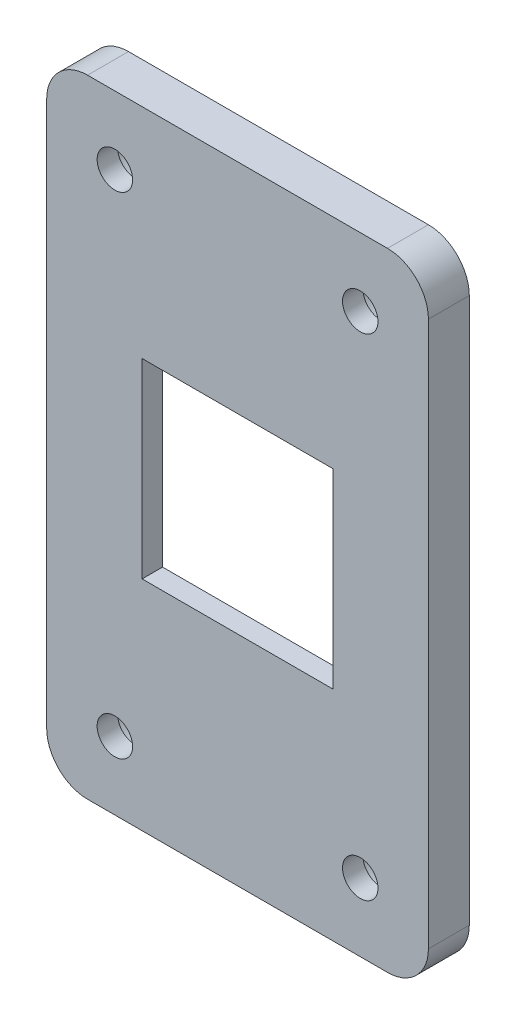
SolidWorks part; units mm, degrees
ref_plane "Front Plane" through (0, 0, 0) normal (1, 0, 0) x (0, 1, 0)
ref_plane "Top Plane" through (0, 0, 0) normal (0, 0, 1) x (0, 1, 0)
ref_plane "Right Plane" through (0, 0, 0) normal (0, 1, 0) x (-1, 0, 0)
sketch "Sketch2" plane through (0, 0, 0) normal (0, 0, 1) x (0, 1, 0)
  line L0 (-10, 10) -> (10, 10)
  line L1 (18, 9) -> (-18, 9) construction
  line L2 (18, 9) -> (18, -9) construction
  line L3 (18, -9) -> (-18, -9) construction
  line L4 (-18, 9) -> (-18, -9) construction
  line L5 (18, 9) -> (-18, -9) construction
  line L6 (18, -9) -> (-18, 9) construction
  line L7 (23, 14) -> (-23, 14)
  line L8 (23, 14) -> (23, -14)
  line L9 (23, -14) -> (-23, -14)
  line L10 (-23, 14) -> (-23, -14)
  line L11 (23, 14) -> (-23, -14) construction
  line L12 (23, -14) -> (-23, 14) construction
  line L13 (-7, 7) -> (7, 7)
  line L14 (-7, 7) -> (-7, -7)
  line L15 (-7, -7) -> (7, -7)
  line L16 (7, 7) -> (7, -7)
  line L17 (-7, 7) -> (7, -7) construction
  line L18 (-7, -7) -> (7, 7) construction
  line L19 (10, 10) -> (10, -10)
  line L20 (-10, -10) -> (10, -10)
  line L21 (-10, 10) -> (-10, -10)
  circle A0 centre (-18, 9) radius 2.5
  circle A1 centre (18, 9) radius 2.5
  circle A2 centre (18, -9) radius 2.5
  circle A3 centre (-18, -9) radius 2.5
  point P0 (0, 0)
  point P6 (0, 0)
  point P16 (0, 0)
  dimension "D5" = 5
  dimension "D1" = 36
  dimension "D2" = 18
  dimension "D3" = 5
  dimension "D4" = 5
  dimension "D6" = 14
  dimension "D7" = 3
extrude "Boss-Extrude1" add sketch "Sketch2" along normal blind 3 contours A3 | L7 L10 L9 L8 A3 A2 A1 A0 | A0 | A1 | A2 | L0 L21 L20 L19 L13 L16 L15 L14 region at (-9.7172, 0, 0) region at (0, 22.4615, 0) region at (-9, -18, 0) region at (-9, 18, 0) region at (9, 18, 0) region at (9, -18, 0)
hole_wizard "Ø2.6 (2.6) Diameter Hole1" positions "Sketch4" profile "Sketch5" hole size "Ø2.6" standard "ANSI Metric" end condition through all
sketch "Sketch4" plane through (0, 0, 0) normal (0, 0, -1) x (-1, 0, 0)
  point P0 (-9, -18)
  point P3 (9, -18)
  point P6 (-9, 18)
  point P9 (9, 18)
sketch "Sketch5" plane through (9, -18, 0) normal (1, 0, 0) x (0, 1, 0)
  line L0 (0, 0) -> (0, 3)
  line L1 (0, 3) -> (1.3, 3)
  line L2 (1.3, 3) -> (1.3, 0)
  line L5 (1.3, 0) -> (0, 0)
  line L11 (0, -6.35) -> (0, 107.95) construction
  dimension "Thru Hole Dia." = 2.6
  dimension "Thru Hole Depth" = 3
extrude "Cut-Extrude2" cut sketch "Sketch2<6>" along normal blind 1.5 contours A3 | A0 | A1 | A2 | L0 L19 L20 L21 region at (-9, -18, 0) region at (-9, 18, 0) region at (9, 18, 0) region at (9, -18, 0)
sketch "Sketch2<6>" plane through (0, 0, 0) normal (0, 0, 1) x (0, 1, 0) same geometry as "Sketch2"
fillet "Fillet1" radius 3 4 edges at (14, 23, 1.5) (14, -23, 1.5) (-14, -23, 1.5) (-14, 23, 1.5)
equation "\"offset\"= 5"
equation "\"D4@Sketch2\"=\"offset\""
equation "\"D3@Sketch2\"=\"offset\""
